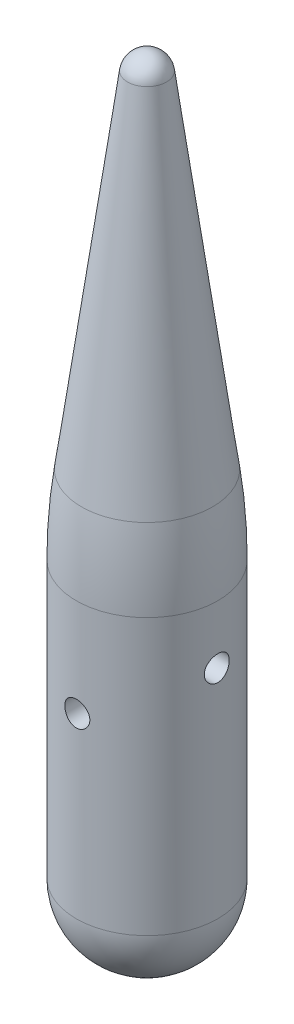
SolidWorks part; units mm, degrees
ref_plane "Front Plane" through (0, 0, 0) normal (1, 0, 0) x (0, 1, 0)
ref_plane "Top Plane" through (0, 0, 0) normal (0, 0, 1) x (0, 1, 0)
ref_plane "Right Plane" through (0, 0, 0) normal (0, 1, 0) x (-1, 0, 0)
sketch "Sketch2" plane through (0, 0, 0) normal (1, 0, 0) x (0, 1, 0)
  line L0 (0, 0) -> (200, 0)
  line L2 (18, 18) -> (88, 18)
  line L3 (108, 16.6697) -> (195.6622, 4.956)
  arc A0 (0, 0) -> (18, 18) centre (18, 0) cw
  arc A1 (200, 0) -> (195.6622, 4.956) centre (195, 0) ccw
  arc A2 (88, 18) -> (108, 16.6697) centre (88, -133.0047) cw
  dimension "D2" = 200
  dimension "D1" = 18
  dimension "D4" = 5
  dimension "D3" = 70
  dimension "D5" = 20
revolve "Revolve1" add sketch "Sketch2" angle 360 about L0
sketch "Sketch3" plane through (0, 0, 0) normal (0, 1, 0) x (-1, 0, 0)
  circle A0 centre (0, 0) radius 6.35
  dimension "D1" = 12.7
extrude "Cut-Extrude1" cut sketch "Sketch3" along normal blind 50
sketch "Sketch4" plane through (0, 0, 0) normal (1, 0, 0) x (0, 1, 0)
  line L0 (0, 0) -> (70, 0) construction
  circle A1 centre (73.175, 0) radius 3.175
  dimension "D2" = 6.35
  dimension "D1" = 70
extrude "Cut-Extrude2" cut sketch "Sketch4" against normal through all both and the other way through all
sketch "Sketch5" plane through (0, 0, 0) normal (0, 0, 1) x (0, 1, 0)
  line L0 (0, 0) -> (60, 0) construction
  circle A0 centre (63.175, 0) radius 3.175
  dimension "D2" = 6.35
  dimension "D1" = 60
extrude "Cut-Extrude3" cut sketch "Sketch5" along normal through all and the other way blind 10
